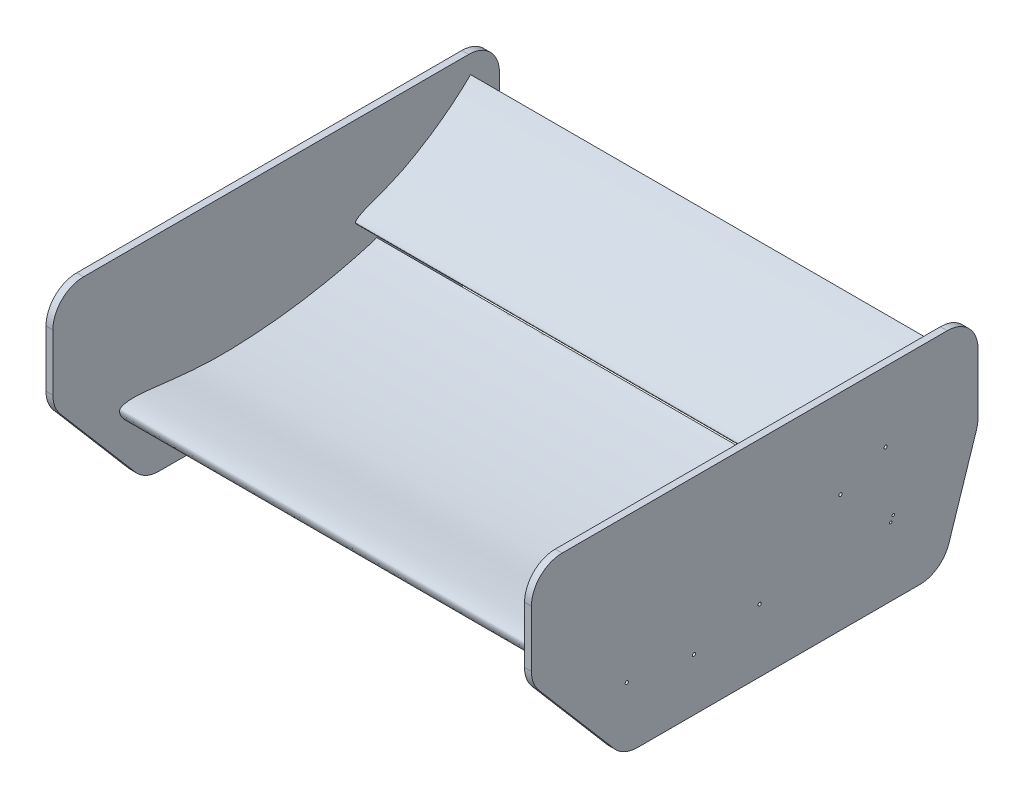
SolidWorks part; units mm, degrees
ref_plane "Front Plane" through (0, 0, 0) normal (0, 0, 1) x (1, 0, 0)
ref_plane "Top Plane" through (0, 0, 0) normal (0, 1, 0) x (1, 0, 0)
ref_plane "Right Plane" through (0, 0, 0) normal (1, 0, 0) x (0, 0, -1)
ref_plane "Soft Top Limit" through (0, 1174.6, 0) normal (0, 1, 0) x (1, 0, 0)
ref_plane "Soft Rear Limit" through (0, 0, -1192.975) normal (0, 0, 1) x (1, 0, 0)
ref_plane "Soft Right Limit" through (-501.65, 0, 0) normal (1, 0, 0) x (0, 0, -1)
ref_plane "Soft Left Limit" through (501.65, 0, 0) normal (1, 0, 0) x (0, 0, -1)
ref_plane "Soft Front Limit" through (0, 0, -165.1) normal (0, 0, 1) x (1, 0, 0)
ref_plane "Slant Limit" through (0, 528.6251, -619.2711) normal (0, -0.6492, 0.7606) x (1, 0, 0)
ref_plane "Bottom" through (0, 476.25, 0) normal (0, 1, 0) x (1, 0, 0)
ref_plane "Midplane" through (0, 0, 0) normal (1, 0, 0) x (0, 0, -1)
curve "Imported Airfoil Curve"
  spline degree 3 poles (0, 2520.0207, 6.126) (0, 2544.889, -1.81) (0, 2521.8965, 7.8839) (0, 2505.3253, 17.7145) (0, 2467.7144, 38.5723) (0, 2424.2142, 62.3813) (0, 2368.0949, 87.8078) (0, 2301.3729, 113.3478) (0, 2223.8362, 140.5377) (0, 2136.6129, 169.2441) (0, 2040.932, 199.097) (0, 1938.2341, 229.6055) (0, 1829.9414, 260.0781) (0, 1717.5266, 289.8586) (0, 1602.4273, 318.1375) (0, 1486.0259, 343.9752) (0, 1369.6902, 366.5754) (0, 1254.3666, 384.7865) (0, 1140.5393, 397.0034) (0, 1028.6357, 403.0127) (0, 919.0585, 402.9406) (0, 812.3986, 397.0375) (0, 709.2785, 385.5985) (0, 610.4299, 369.039) (0, 516.5862, 348.1086) (0, 428.5874, 323.3415) (0, 347.2653, 295.2055) (0, 273.332, 264.2656) (0, 207.4209, 231.0894) (0, 150.0337, 196.3024) (0, 101.596, 160.572) (0, 62.3674, 124.65) (0, 32.4977, 89.3959) (0, 12.0597, 55.6746) (0, 1.683, 26.6201) (0, -0.5567, 6.5526) (0, 0.5894, -3.9947) (0, 1.6947, -9.1451) (0, 2.8711, -12.4915) (0, 3.9449, -14.9776) (0, 4.8993, -16.669) (0, 5.9763, -18.2433) (0, 7.3264, -19.6365) (0, 8.8595, -20.9434) (0, 11.1868, -22.7306) (0, 14.6073, -24.7406) (0, 20.085, -27.4067) (0, 26.8353, -29.9257) (0, 44.6446, -35.1819) (0, 77.8093, -38.8998) (0, 130.2841, -38.2927) (0, 196.3018, -31.4611) (0, 276.2192, -18.4434) (0, 370.8288, 0.8611) (0, 480.7331, 24.811) (0, 605.9792, 50.0099) (0, 745.0759, 74.1542) (0, 895.4497, 95.0846) (0, 1053.6786, 110.004) (0, 1215.6439, 118.3392) (0, 1377.6893, 121.6348) (0, 1537.1174, 120.5125) (0, 1691.5141, 115.2051) (0, 1838.3121, 105.7388) (0, 1975.028, 93.0069) (0, 2099.5942, 78.4581) (0, 2210.5746, 63.1262) (0, 2306.3634, 48.0168) (0, 2387.2069, 33.7158) (0, 2449.0745, 22.0129) (0, 2499.1865, 10.4993) (0, 2520.0207, 6.126) (0, 2544.889, -1.81) (0, 2521.8965, 7.8839) knots -0.016237 -0.007308 -0.001841 0 0.001813 0.006911 0.014576 0.024172 0.035572 0.049013 0.064513 0.081849 0.100772 0.120997 0.142228 0.164173 0.186537 0.209023 0.231367 0.25332 0.274804 0.295858 0.316449 0.336531 0.356033 0.374893 0.39299 0.410197 0.426388 0.441459 0.455334 0.467938 0.479236 0.489204 0.497851 0.505194 0.511308 0.515097 0.516441 0.517273 0.51806 0.518436 0.518797 0.519154 0.519508 0.519887 0.520289 0.52116 0.522116 0.52372 0.525214 0.532575 0.542381 0.554776 0.569931 0.588005 0.609188 0.633329 0.660001 0.688743 0.718873 0.749543 0.780127 0.810209 0.839387 0.867183 0.893104 0.91676 0.937874 0.956199 0.971544 0.983763 0.992692 0.998159 1 1.001813 1.006911 1.014576 periodic
sketch "Airfoils Sketch" plane through (0, 0, 0) normal (1, 0, 0) x (0, 0, -1)
  line L0 (165.1, 1174.6) -> (165.1, 1060.6753) construction
  line L1 (165.1, 1060.6753) -> (663.9798, 476.25) construction
  line L2 (663.9798, 476.25) -> (1192.975, 476.25) construction
  line L3 (1192.975, 476.25) -> (1192.975, 1174.6) construction
  line L4 (1192.975, 1174.6) -> (165.1, 1174.6) construction
  line L5 (509.9361, 1174.6) -> (-509.9361, 1174.6) construction
  line L6 (165.1, 67.0076) -> (165.1, -67.0076) construction
  line L7 (364.7288, 826.8151) -> (873.8134, 230.4351) construction
  line L8 (279.3831, 476.25) -> (-279.3831, 476.25) construction
  line L9 (1192.975, 353.2696) -> (1192.975, -353.2696) construction
  line L10 (414.7055, 818.0274) -> (401.202, 972.3726) construction
  line L11 (945.202, 874.5029) -> (933.446, 1008.8748) construction
  line L12 (939.324, 941.6889) -> (407.9538, 895.2) construction
  line L13 (306.3538, 895.2) -> (1192.975, 895.2) construction
  line L14 (866.0383, 1036.8746) -> (926.5682, 940.0065) construction
  line L15 (1102.685, 1185.4108) -> (1163.8108, 1087.5892) construction
  line L16 (1133.2479, 1136.5) -> (896.3033, 988.4406) construction
  line L21 (176.2614, 1047.6) -> (1192.975, 1047.6) construction
  spline S0 degree 3 poles (935.2529, 940.0507) (940.3147, 942.1548) (935.6767, 939.7163) (932.3848, 937.3638) (924.8872, 932.3286) (916.21, 926.5709) (904.9213, 920.2497) (891.4161, 913.7156) (875.6775, 906.6433) (857.9391, 899.0809) (838.4515, 891.1278) (817.5075, 882.9123) (795.3921, 874.6046) (772.4019, 866.3681) (748.8232, 858.3979) (724.9284, 850.9153) (700.9897, 844.1113) (677.1845, 838.2437) (653.5854, 833.657) (630.2782, 830.4035) (607.3492, 828.4639) (584.9266, 827.7965) (563.1459, 828.3505) (542.1676, 830.0521) (522.1586, 832.7575) (503.3041, 836.37) (485.7865, 840.8065) (469.765, 845.9615) (455.382, 851.7275) (442.7539, 857.9825) (431.9816, 864.5947) (423.1327, 871.4111) (416.2539, 878.2548) (411.376, 884.946) (408.6865, 890.8402) (407.8599, 894.9991) (407.9116, 897.2265) (408.051, 898.3239) (408.2374, 899.0451) (408.4178, 899.5844) (408.5873, 899.9553) (408.7846, 900.3039) (409.0422, 900.6195) (409.3397, 900.9203) (409.7947, 901.3358) (410.4746, 901.8174) (411.5732, 902.4729) (412.9407, 903.1204) (416.5733, 904.5379) (423.4463, 905.9074) (434.4368, 906.7165) (448.3721, 906.4646) (465.3261, 905.1664) (485.4664, 902.8148) (508.8897, 899.7641) (535.5455, 896.7257) (565.0805, 894.155) (596.9177, 892.4579) (630.2914, 892.1587) (664.3294, 893.3038) (698.2942, 895.5048) (731.6326, 898.5836) (763.8436, 902.4482) (794.3904, 907.0475) (822.7695, 912.1503) (848.5739, 917.4165) (871.5218, 922.6042) (891.2949, 927.4743) (907.9553, 931.9087) (920.6916, 935.461) (930.9716, 938.764) (935.2529, 940.0507) (940.3147, 942.1548) (935.6767, 939.7163) knots -0.016237 -0.007308 -0.001841 0 0.001813 0.006911 0.014576 0.024172 0.035572 0.049013 0.064513 0.081849 0.100772 0.120997 0.142228 0.164173 0.186537 0.209023 0.231367 0.25332 0.274804 0.295858 0.316449 0.336531 0.356033 0.374893 0.39299 0.410197 0.426388 0.441459 0.455334 0.467938 0.479236 0.489204 0.497851 0.505194 0.511308 0.515097 0.516441 0.517273 0.51806 0.518436 0.518797 0.519154 0.519508 0.519887 0.520289 0.52116 0.522116 0.52372 0.525214 0.532575 0.542381 0.554776 0.569931 0.588005 0.609188 0.633329 0.660001 0.688743 0.718873 0.749543 0.780127 0.810209 0.839387 0.867183 0.893104 0.91676 0.937874 0.956199 0.971544 0.983763 0.992692 0.998159 1 1.001813 1.006911 1.014576 only from (939.324, 941.6889) to (939.324, 941.6889)
  spline S1 degree 3 poles (1131.7374, 1134.7673) (1133.5995, 1136.953) (1132.0147, 1134.712) (1131.0377, 1132.8312) (1128.7359, 1128.6983) (1126.0553, 1123.9476) (1122.2899, 1118.3128) (1117.5406, 1112.0516) (1111.8769, 1105.0082) (1105.3965, 1097.2604) (1098.1926, 1088.9143) (1090.3713, 1080.0994) (1082.0253, 1070.9629) (1073.254, 1061.6516) (1064.1447, 1052.3247) (1054.7721, 1043.1501) (1045.2175, 1034.2818) (1035.5025, 1025.8823) (1025.5791, 1018.1297) (1015.4749, 1011.0686) (1005.2348, 1004.7108) (994.9285, 999.0671) (984.6313, 994.1461) (974.4357, 989.9515) (964.4538, 986.456) (954.795, 983.6583) (945.5642, 981.5631) (936.8608, 980.159) (928.7768, 979.4298) (921.3956, 979.3461) (914.7955, 979.8704) (909.0446, 980.9475) (904.2067, 982.5058) (900.3389, 984.4687) (897.682, 986.58) (896.3072, 988.3245) (895.8017, 989.3763) (895.6058, 989.9216) (895.5213, 990.3026) (895.4772, 990.5972) (895.4681, 990.8106) (895.4773, 991.0202) (895.5225, 991.2288) (895.5898, 991.4399) (895.7034, 991.742) (895.9061, 992.1285) (896.263, 992.6957) (896.7472, 993.3231) (898.1055, 994.8485) (900.9876, 997.1221) (905.9247, 1000.1133) (912.4884, 1003.3096) (920.7099, 1006.7355) (930.6689, 1010.4274) (942.3265, 1014.5737) (955.4898, 1019.4945) (969.8856, 1025.3183) (985.1482, 1032.0973) (1000.7954, 1039.894) (1016.4092, 1048.5229) (1031.7378, 1057.6271) (1046.5653, 1066.992) (1060.6797, 1076.4556) (1073.8427, 1085.8664) (1085.8742, 1094.9966) (1096.6653, 1103.5909) (1106.1418, 1111.4691) (1114.2121, 1118.4443) (1120.9333, 1124.4758) (1126.0328, 1129.1625) (1130.0452, 1133.1487) (1131.7374, 1134.7673) (1133.5995, 1136.953) (1132.0147, 1134.712) knots -0.016237 -0.007308 -0.001841 0 0.001813 0.006911 0.014576 0.024172 0.035572 0.049013 0.064513 0.081849 0.100772 0.120997 0.142228 0.164173 0.186537 0.209023 0.231367 0.25332 0.274804 0.295858 0.316449 0.336531 0.356033 0.374893 0.39299 0.410197 0.426388 0.441459 0.455334 0.467938 0.479236 0.489204 0.497851 0.505194 0.511308 0.515097 0.516441 0.517273 0.51806 0.518436 0.518797 0.519154 0.519508 0.519887 0.520289 0.52116 0.522116 0.52372 0.525214 0.532575 0.542381 0.554776 0.569931 0.588005 0.609188 0.633329 0.660001 0.688743 0.718873 0.749543 0.780127 0.810209 0.839387 0.867183 0.893104 0.91676 0.937874 0.956199 0.971544 0.983763 0.992692 0.998159 1 1.001813 1.006911 1.014576 only from (1133.2479, 1136.5) to (1133.2479, 1136.5)
  dimension "D1" = 533.4
  dimension "D2" = 279.4
  dimension "D3" = 5
  dimension "D4" = 101.6
  dimension "D5" = 279.4
  dimension "D6" = 38.1
  dimension "D7" = 32
  dimension "D8" = 59.7271
  dimension "D9" = 127
extrude "Extruded Airfoils" add sketch "Airfoils Sketch" along normal offset from surface (487.45 mm away) 14.2 up to plane "Soft Left Limit"
sketch "Endplate Sketch" plane through (501.65, 0, 0) normal (1, 0, 0) x (0, 0, -1)
  line L6 (333.4477, 1174.6) -> (1129.475, 1174.6)
  line L7 (1192.975, 1174.6) -> (165.1, 1174.6) construction
  line L8 (1192.975, 1111.1) -> (1192.975, 986.6717)
  line L9 (1192.975, 476.25) -> (1192.975, 1174.6) construction
  line L11 (1189.8464, 966.9854) -> (1132.8969, 792.34)
  line L12 (1072.5255, 748.5263) -> (489.1772, 748.5263)
  line L19 (440.8805, 770.7991) -> (285.151, 953.2323)
  line L26 (269.9477, 994.4595) -> (269.9477, 1111.1)
  line L28 (165.1, 1060.6753) -> (663.9798, 476.25) construction
  arc A12 (1129.475, 1174.6) -> (1192.975, 1111.1) centre (1129.475, 1111.1) cw
  arc A13 (1192.975, 986.6717) -> (1189.8464, 966.9854) centre (1129.475, 986.6717) cw
  arc A14 (1132.8969, 792.34) -> (1072.5255, 748.5263) centre (1072.5255, 812.0263) cw
  arc A15 (489.1772, 748.5263) -> (440.8805, 770.7991) centre (489.1772, 812.0263) cw
  arc A16 (285.151, 953.2323) -> (269.9477, 994.4595) centre (333.4477, 994.4595) cw
  arc A17 (333.4477, 1174.6) -> (269.9477, 1111.1) centre (333.4477, 1111.1) ccw
  point P16 (1192.975, 1174.6)
  point P19 (1192.975, 976.5799)
  point P29 (269.9477, 1174.6)
  dimension "D1" = 63.5
extrude "Extruded Endplate" add sketch "Endplate Sketch" against normal up to surface (14.2 mm away)
mirror "Mirror" about plane through (0, 0, 0) normal (1, 0, 0) of bodies 106
sketch "Sketch1" plane through (501.65, 0, 0) normal (1, 0, 0) x (0, 0, -1)
  circle A0 centre (466.9636, 876.0274) radius 3.302
extrude "Cut-Extrude1" cut sketch "Sketch1" against normal up to surface (14.2 mm away) up to face at (487.45, 961.8886, -750.0842)
sketch "Sketch2" plane through (501.65, 0, 0) normal (1, 0, 0) x (0, 0, -1)
  circle A0 centre (605.9718, 856.7319) radius 3.302
extrude "Cut-Extrude2" cut sketch "Sketch2" against normal up to surface (14.2 mm away) up to face at (487.45, 961.8886, -750.0842)
sketch "Sketch3" plane through (501.65, 0, 0) normal (1, 0, 0) x (0, 0, -1)
  circle A0 centre (741.5917, 878.9853) radius 3.302
  circle A1 centre (908.6976, 991.5292) radius 3.302
  circle A2 centre (1002.03, 1029.97) radius 3.302
extrude "Cut-Extrude3" cut sketch "Sketch3" against normal up to surface (14.2 mm away) up to face at (487.45, 961.8886, -750.0842)
sketch "Sketch4" plane through (501.65, 0, 0) normal (1, 0, 0) x (0, 0, -1)
  circle A0 centre (1018.0658, 900.3059) radius 2.54
  circle A1 centre (1012.4254, 889.9969) radius 2.54
extrude "Cut-Extrude4" cut sketch "Sketch4" against normal up to surface (14.2 mm away) up to face at (487.45, 961.8886, -750.0842)
